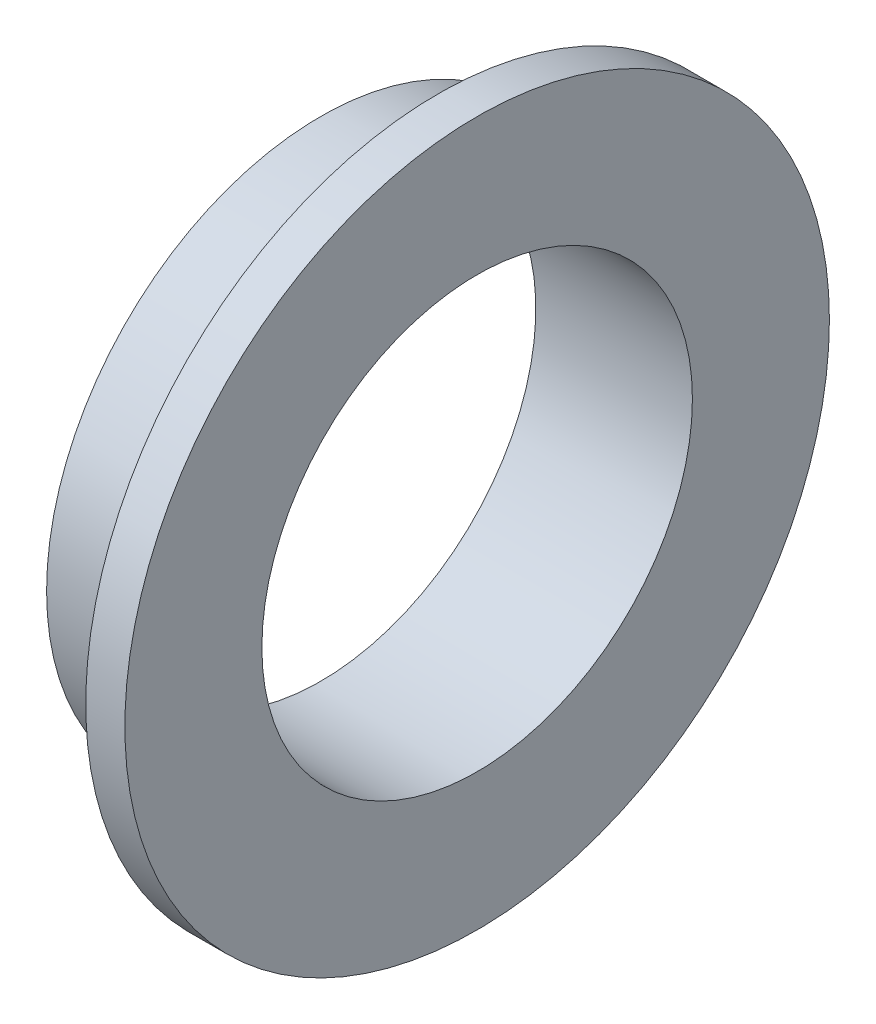
SolidWorks part; units mm, degrees
material "7075-T6 (SN)"
ref_plane "Front Plane" through (0, 0, 0) normal (0, 0, 1) x (1, 0, 0)
ref_plane "Top Plane" through (0, 0, 0) normal (0, 1, 0) x (1, 0, 0)
ref_plane "Right Plane" through (0, 0, 0) normal (1, 0, 0) x (0, 0, -1)
sketch "Sketch1" plane through (0, 0, 0) normal (1, 0, 0) x (0, 0, -1)
  circle A0 centre (0, 0) radius 34.925
  circle A1 centre (0, 0) radius 57.15
  dimension "D1" = 69.85
  dimension "D2" = 114.3
extrude "Boss-Extrude1" add sketch "Sketch1" along normal blind 6.35
sketch "Sketch2" plane through (0, 0, 0) normal (-1, 0, 0) x (0, 0, 1)
  circle A0 centre (0, 0) radius 44.45
  circle A1 centre (0, 0) radius 34.925
  dimension "D1" = 88.9
extrude "Boss-Extrude2" add sketch "Sketch2" along normal blind 19.05
